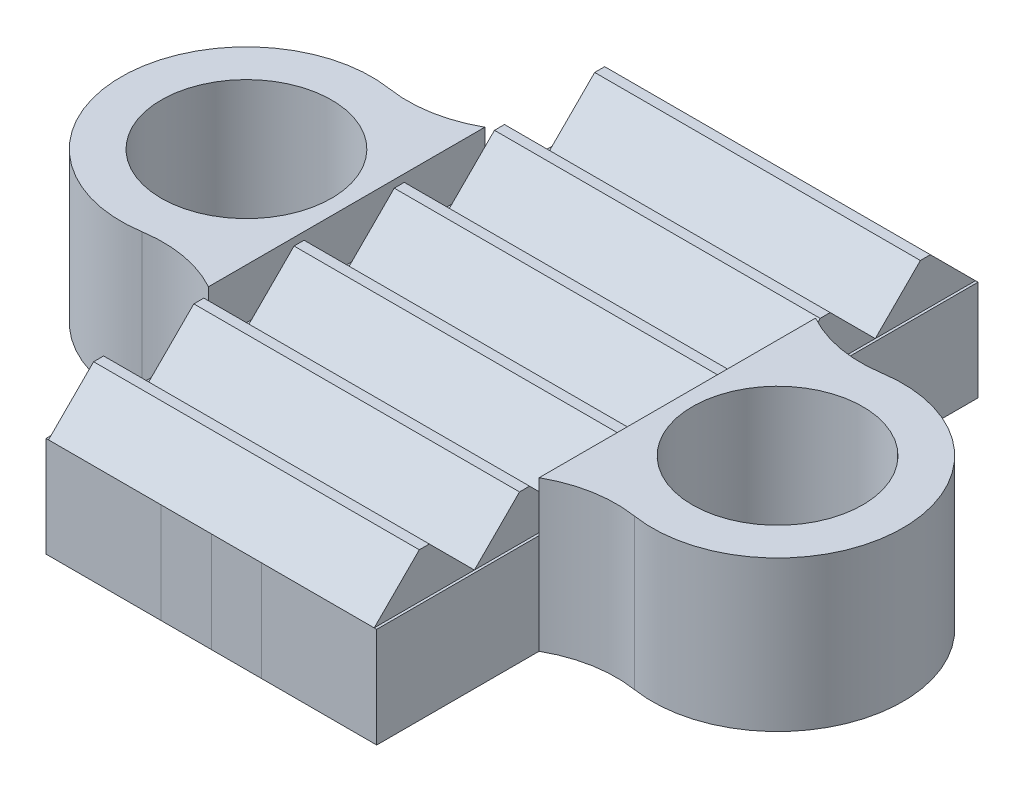
SolidWorks part; units mm, degrees
ref_plane "Alzado" through (0, 0, 0) normal (0, 0, 1) x (1, 0, 0)
ref_plane "Planta" through (0, 0, 0) normal (0, 1, 0) x (1, 0, 0)
ref_plane "Vista lateral" through (0, 0, 0) normal (1, 0, 0) x (0, 0, -1)
sketch "Croquis1" plane through (0, 0, 0) normal (0, 1, 0) x (1, 0, 0)
  line L0 (0, -16.4018) -> (0, 78.9163) construction
  line L1 (-63.9099, 0) -> (63.9099, 0) construction
  line L2 (-3.3, 6) -> (3.3, 6)
  line L3 (3.3, 6) -> (3.3, 2.7581)
  line L4 (-3.3, -6) -> (3.3, -6)
  line L5 (3.3, -6) -> (3.3, -2.7581)
  line L6 (-3.3, -6) -> (-3.3, -2.7581)
  line L7 (-3.3, 6) -> (-3.3, 2.7581)
  line L8 (3.3, -2.7581) -> (3.3, 2.7581)
  line L9 (-3.3, -2.7581) -> (-3.3, 2.7581)
  circle A0 centre (5.3, 0) radius 1.7
  arc A1 (4.911, -2.4695) -> (4.911, 2.4695) centre (5.3, 0) ccw
  arc A2 (3.3, 2.7581) -> (4.911, 2.4695) centre (4.5219, 4.9391) ccw
  arc A3 (3.3, -2.7581) -> (4.911, -2.4695) centre (4.5219, -4.9391) cw
  arc A4 (-3.3, -2.7581) -> (-4.911, -2.4695) centre (-4.5219, -4.9391) ccw
  arc A5 (-3.3, 2.7581) -> (-4.911, 2.4695) centre (-4.5219, 4.9391) cw
  arc A6 (-4.911, -2.4695) -> (-4.911, 2.4695) centre (-5.3, 0) cw
  circle A7 centre (-5.3, 0) radius 1.7
  point P6 (7.8, 0)
  point P10 (8, 0)
  point P19 (0, 0)
  point P28 (0, -6)
  point P29 (-8, 0)
  point P30 (0, 6)
  dimension "D1" = 7.8
  dimension "D5" = 5
  dimension "D6" = 5
  dimension "D4" = 6
extrude "Saliente-Extruir1" add sketch "Croquis1" along normal blind 2 contours L9 L6 L4 L5 L8 L3 L2 L7 | L8 A3 A1 A2 A0 | A6 A4 L9 A5 A7 region at (0, 0, 0) region at (-3.3712, 0, 0) region at (4.0687, 0, -2.4082)
ref_plane "Plano1" through (3.25, 0, 0) normal (1, 0, 0) x (0, 0, -1)
sketch "Croquis4" plane through (3.25, 0, 0) normal (1, 0, 0) x (0, 0, -1)
  line L0 (-6, 2) -> (-4, 2)
  line L1 (-6, 2) -> (-5.1, 2.9)
  line L2 (-5, 3) -> (-5, 2) construction
  line L3 (-4, 2) -> (-4.9, 2.9)
  line L4 (-5.1, 2.9) -> (-4.9, 2.9)
  dimension "D1" = 1
  dimension "D2" = 1
  dimension "D3" = 0.9
extrude "Saliente-Extruir2" add sketch "Croquis4" against normal blind 6.5
pattern_linear "MatrizL1" count 6 spacing 2 along (0, 0, -1) of "Saliente-Extruir2"
sketch "Sketch1" plane through (0, 0, 6) normal (0, 0, 1) x (1, 0, 0)
  line L0 (0, 2) -> (0, 0)
  line L1 (-3.25, 2) -> (3.25, 2) construction
  line L4 (-1, 2) -> (1, 2)
  line L5 (-1, 2) -> (-1, 0)
  line L6 (-1, 0) -> (1, 0)
  line L7 (1, 2) -> (1, 0)
  line M7 (3.25, 2) -> (-3.25, 2)
  dimension "D1" = 1
  dimension "D2" = 1
extrude "Cut-Extrude1" cut sketch "Sketch1" against normal blind 0.1 contours L7 L0 M7 | L5 L0 M7 region at (0.5, 1, 6) region at (-0.5, 1, 6)
extrude "Boss-Extrude1" add sketch "Sketch1<3>" against normal blind 0.1 separate body contours L7 L0 M7 region at (0.5, 1, 6)
sketch "Sketch1<3>" plane through (0, 0, 6) normal (0, 0, 1) x (1, 0, 0) same geometry as "Sketch1"
extrude "Boss-Extrude2" add sketch "Sketch1<4>" against normal blind 0.1 separate body contours L5 L0 M7 region at (-0.5, 1, 6)
sketch "Sketch1<4>" plane through (0, 0, 6) normal (0, 0, 1) x (1, 0, 0) same geometry as "Sketch1"
extrude "Boss-Extrude3" add sketch "Croquis1<4>" along normal blind 1 from surface contours A6 A4 L9 A5 A7 | L8 A3 A1 A2 A0 region at (-3.3712, 0, 0) region at (4.0687, 0, -2.4082) starting at face at (-5.3, 2, 1.7)
sketch "Croquis1<4>" plane through (0, 0, 0) normal (0, 1, 0) x (1, 0, 0) same geometry as "Croquis1"
